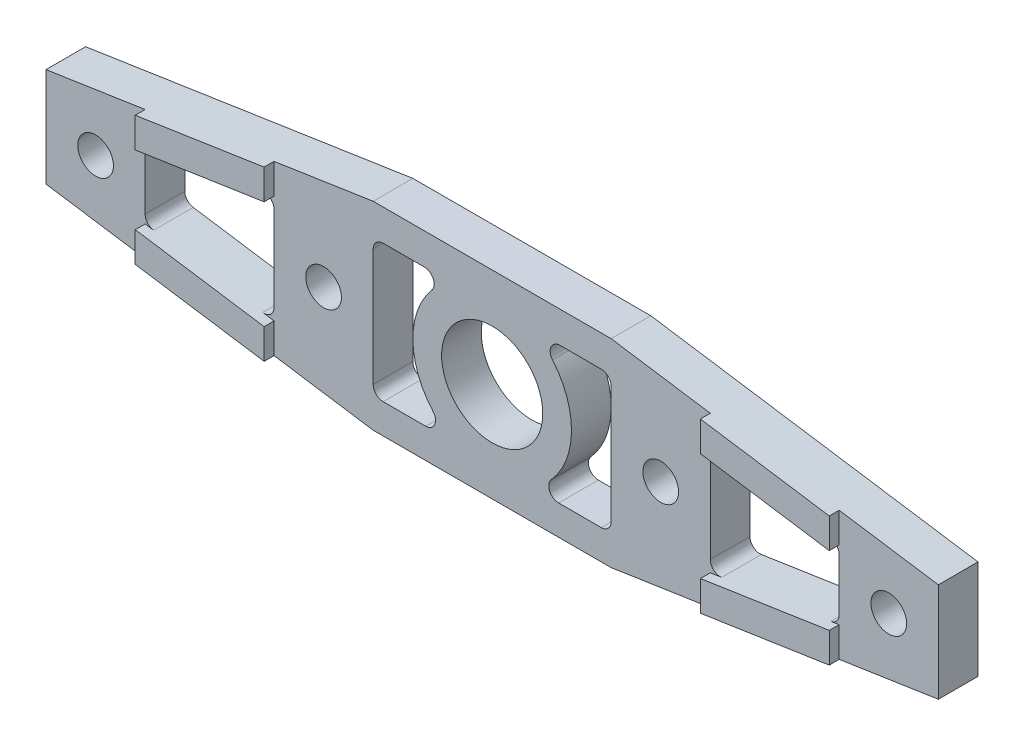
SolidWorks part; units mm, degrees
ref_plane "正面" through (0, 0, 0) normal (0, 0, 1) x (1, 0, 0)
ref_plane "平面" through (0, 0, 0) normal (0, 1, 0) x (1, 0, 0)
ref_plane "右側面" through (0, 0, 0) normal (1, 0, 0) x (0, 0, -1)
sketch "ｽｹｯﾁ1" plane through (0, 0, 0) normal (0, 0, 1) x (1, 0, 0)
  line L1 (-45, 10) -> (45, 10)
  line L2 (-45, 10) -> (-45, -10)
  line L3 (-45, -10) -> (45, -10)
  line L4 (45, 10) -> (45, -10)
  line L5 (-45, 10) -> (45, -10) construction
  line L6 (-45, -10) -> (45, 10) construction
  point P0 (0, 0)
  dimension "D1" = 90
  dimension "D2" = 20
extrude "ﾎﾞｽ - 押し出し1" add sketch "ｽｹｯﾁ1" along normal blind 4
sketch "ｽｹｯﾁ2" plane through (0, 0, 4) normal (0, 0, 1) x (1, 0, 0)
  line L0 (45, 10) -> (-45, 10) construction
  line L1 (-35, 10) -> (-22, 10)
  line L2 (-35, 10) -> (-35, -10)
  line L3 (-35, -10) -> (-22, -10)
  line L4 (-22, 10) -> (-22, -10)
  line L5 (-45, -10) -> (45, -10) construction
  line L6 (-45, 10) -> (-45, -10) construction
  line L7 (22, 10) -> (35, 10)
  line L8 (22, 10) -> (22, -10)
  line L9 (22, -10) -> (35, -10)
  line L10 (35, 10) -> (35, -10)
  line L11 (45, -10) -> (45, 10) construction
  dimension "D1" = 10
  dimension "D2" = 10
  dimension "D3" = 22
  dimension "D4" = 22
extrude "ﾎﾞｽ - 押し出し2" add sketch "ｽｹｯﾁ2" along normal blind 1
sketch "ｽｹｯﾁ4" plane through (0, 0, 4) normal (0, 0, 1) x (1, 0, 0)
  circle A0 centre (0, 0) radius 5.1
  dimension "D1" = 10.2
extrude "ﾎﾞｽ - 押し出し3" add sketch "ｽｹｯﾁ4" against normal up to surface (4 mm away) up to face at (0, 0, 0)
sketch "ｽｹｯﾁ3" plane through (0, 0, 4) normal (0, 0, 1) x (1, 0, 0)
  line L0 (-45, 0) -> (45, 0) construction
  line L1 (-45, 10) -> (-45, -10) construction
  line L2 (45, -10) -> (45, 10) construction
  line L3 (-35, 10) -> (-35, -10) construction
  line L4 (-22, -10) -> (-22, 10) construction
  line L5 (22, 10) -> (22, -10) construction
  line L6 (35, -10) -> (35, 10) construction
  circle A0 centre (-40, 0) radius 1.8
  circle A1 centre (-17, 0) radius 1.8
  circle A2 centre (17, 0) radius 1.8
  circle A3 centre (40, 0) radius 1.8
  dimension "D1" = 3.6
  dimension "D2" = 5
  dimension "D3" = 5
  dimension "D4" = 5
  dimension "D5" = 5
extrude "ｶｯﾄ - 押し出し1" cut sketch "ｽｹｯﾁ3" against normal through all
extrude "ｶｯﾄ - 押し出し3" cut sketch "ｽｹｯﾁ4<3>" against normal through all contours A0
sketch "ｽｹｯﾁ4<3>" plane through (0, 0, 4) normal (0, 0, 1) x (1, 0, 0) same geometry as "ｽｹｯﾁ4"
sketch "ｽｹｯﾁ7" plane through (0, 0, 0) normal (0, 0, -1) x (-1, 0, 0)
  line L0 (-45, 5) -> (-45, -5)
  line L1 (-45, -10) -> (-45, 10) construction
  line L2 (-45, -5) -> (-12, -10)
  line L3 (45, -10) -> (-45, -10) construction
  line L4 (-12, -10) -> (12, -10)
  line L5 (12, -10) -> (45, -5)
  line L6 (45, 10) -> (45, -10) construction
  line L7 (45, -5) -> (45, 5)
  line L8 (45, 5) -> (12, 10)
  line L9 (-45, 10) -> (45, 10) construction
  line L10 (12, 10) -> (-12, 10)
  line L11 (-12, 10) -> (-45, 5)
  dimension "D1" = 10
  dimension "D2" = 5
  dimension "D3" = 5
  dimension "D4" = 12
  dimension "D5" = 12
  dimension "D6" = 12
  dimension "D7" = 12
extrude "ｶｯﾄ - 押し出し6" cut sketch "ｽｹｯﾁ7" against normal blind 10 flip side to cut
sketch "ｽｹｯﾁ8" plane through (0, 0, 5) normal (0, 0, 1) x (1, 0, 0)
  line L0 (22, 5.4506) -> (22, -5.4506)
  line L1 (22, -5.4506) -> (35, -3.4809)
  line L2 (35, -3.4809) -> (35, 3.4809)
  line L3 (35, 3.4809) -> (22, 5.4506)
  line L4 (35, 6.5152) -> (22, 8.4848) construction
  line L5 (22, -8.4848) -> (35, -6.5152) construction
  line L6 (35, -6.5152) -> (35, 6.5152) construction
  line L7 (22, 8.4848) -> (22, -8.4848) construction
  line L8 (-22, 5.4506) -> (-35, 3.4809)
  line L9 (-22, -8.4848) -> (-22, 8.4848) construction
  line L10 (-35, 6.5152) -> (-35, -6.5152) construction
  line L11 (-35, 3.4809) -> (-35, -3.4809)
  line L12 (-35, -3.4809) -> (-22, -5.4506)
  line L13 (-22, -5.4506) -> (-22, 5.4506)
  line L14 (-22, 8.4848) -> (-35, 6.5152) construction
  line L15 (-35, -6.5152) -> (-22, -8.4848) construction
  dimension "D1" = 3
  dimension "D2" = 3
  dimension "D3" = 3
  dimension "D4" = 3
extrude "ｶｯﾄ - 押し出し7" cut sketch "ｽｹｯﾁ8" against normal through all
sketch "ｽｹｯﾁ9" plane through (0, 0, 4) normal (0, 0, 1) x (1, 0, 0)
  line L0 (-12, 6.8373) -> (-12, -7)
  line L1 (-12, -7) -> (-3.873, -7)
  line L2 (-12, 6.8373) -> (-4.1535, 6.8373)
  line L3 (-22, -5.4506) -> (-22, 5.4506) construction
  line L4 (-12, -10) -> (12, -10) construction
  line L5 (4.1535, 6.8373) -> (12, 6.8373)
  line L6 (12, 6.8373) -> (12, -7)
  line L7 (12, -7) -> (3.873, -7)
  line L8 (22, 5.4506) -> (22, -5.4506) construction
  arc A0 (-4.1535, 6.8373) -> (-3.873, -7) centre (0, 0) ccw
  arc A1 (3.873, -7) -> (4.1535, 6.8373) centre (0, 0) ccw
  point P10 (-7.9984, -0.1622)
  dimension "D4" = 8
  dimension "D1" = 10
  dimension "D2" = 8
  dimension "D3" = 3
  dimension "D5" = 3
  dimension "D6" = 10
extrude "ｶｯﾄ - 押し出し8" cut sketch "ｽｹｯﾁ9" against normal through all
fillet "ﾌｨﾚｯﾄ1" radius 1 16 edges at (-3.873, -7, 2) (3.873, -7, 2) (4.1535, 6.8373, 2) (-4.1535, 6.8373, 2) (-12, 6.8373, 2) (12, 6.8373, 2) (12, -7, 2) (22, -5.4506, 2) (22, 5.4506, 2) (35, 3.4809, 2) (35, -3.4809, 2) (-12, -7, 2) (-22, 5.4506, 2) (-35, 3.4809, 2) (-35, -3.4809, 2) (-22, -5.4506, 2)
